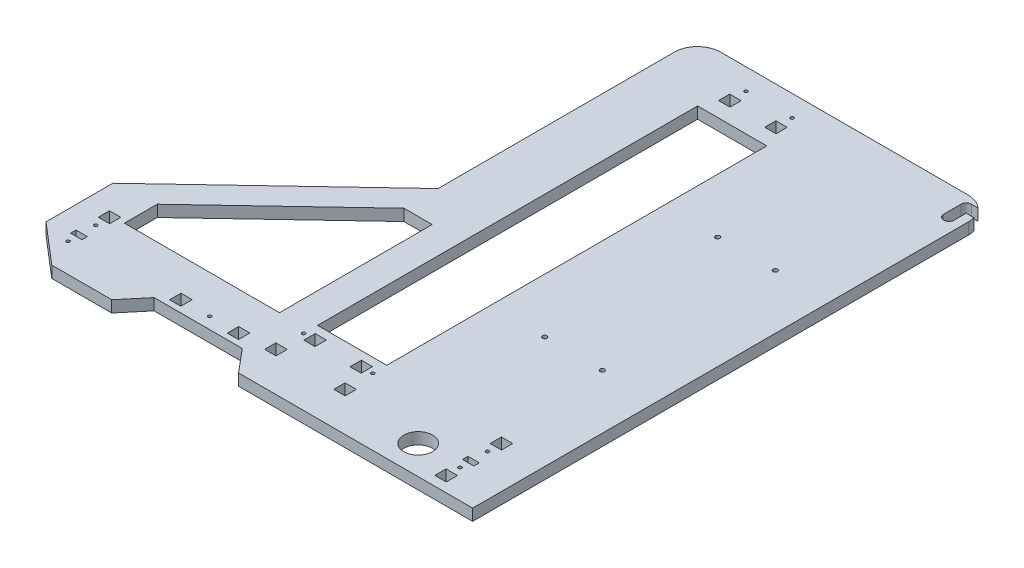
SolidWorks part; units mm, degrees
ref_plane "Front Plane" through (0, 0, 0) normal (0, 0, 1) x (1, 0, 0)
ref_plane "Top Plane" through (0, 0, 0) normal (0, 1, 0) x (1, 0, 0)
ref_plane "Right Plane" through (0, 0, 0) normal (1, 0, 0) x (0, 0, -1)
sketch "Sketch1" plane through (0, 0, 0) normal (0, 1, 0) x (1, 0, 0)
  line L0 (0, 0) -> (-235, 0)
  line L1 (-235, 0) -> (-235, -225)
  line L2 (-235, -225) -> (-380, -362)
  line L3 (-380, -362) -> (-380, -420)
  line L4 (-380, -420) -> (-345, -450)
  line L5 (-345, -450) -> (-293, -450)
  line L6 (-293, -450) -> (-263.6315, -415)
  line L7 (-263.6315, -415) -> (-212.3685, -415)
  line L8 (-212.3685, -415) -> (-183, -450)
  line L9 (-183, -450) -> (0, -450)
  line L10 (0, 0) -> (0, -450)
  line L12 (-293, -450) -> (-183, -450) construction
  dimension "D3" = 235
  dimension "D5" = 58
  dimension "D13" = 190
  dimension "D7" = 35
  dimension "D15" = 52
  dimension "D12" = 30
  dimension "D10" = 35
  dimension "D6" = 380
  dimension "D4" = 450
  dimension "D2" = 50
  dimension "D8" = 50
  dimension "D9" = 110
extrude "Boss-Extrude1" add sketch "Sketch1" along normal blind 10
sketch "Sketch16" plane through (0, 10, 0) normal (0, 1, 0) x (1, 0, 0)
  line L0 (0, -450) -> (20, -450)
  line L1 (20, -450) -> (20, 0)
  line L2 (20, 0) -> (0, 0)
  line L3 (0, 0) -> (0, -450)
  dimension "D1" = 20
  dimension "D2" = 90
extrude "Boss-Extrude2" add sketch "Sketch16" against normal through all
sketch "Sketch2" plane through (0, 10, 0) normal (0, 1, 0) x (1, 0, 0)
  line L0 (-235, -225) -> (-235, -415) construction
  line L1 (-263.6315, -415) -> (-212.3685, -415) construction
  line L2 (-345, -450) -> (-345, -328.931) construction
  line L3 (-235, -225) -> (-380, -362) construction
  line L4 (-345, -358.5097) -> (-235, -254.5787)
  line L5 (-235, -254.5787) -> (-210.5, -254.5787)
  line L6 (-210.5, -254.5787) -> (-210.5, -387)
  line L7 (-210.5, -387) -> (-345, -387)
  line L8 (-345, -387) -> (-345, -358.5097)
  line L9 (0, -450) -> (0, 0) construction
  line L10 (-184.5, -380) -> (-124.5, -380)
  line L11 (-184.5, -380) -> (-184.5, -50.425)
  line L12 (-184.5, -50.425) -> (-124.5, -50.425)
  line L13 (-124.5, -380) -> (-124.5, -50.425)
  line L14 (-124.5, -392.1) -> (-184.5, -392.1) construction
  line L15 (-16, -450) -> (-16, 0) construction
  line L16 (20, 0) -> (-235, 0) construction
  line L17 (-355.9, -440.6571) -> (-355.9, -339.2297) construction
  line L18 (-20.925, -441.85) -> (-11.075, -441.85)
  line L19 (-20.925, -441.85) -> (-20.925, -432.15)
  line L20 (-20.925, -432.15) -> (-11.075, -432.15)
  line L21 (-11.075, -441.85) -> (-11.075, -432.15)
  line L22 (-20.925, -441.85) -> (-11.075, -432.15) construction
  line L23 (-20.925, -432.15) -> (-11.075, -441.85) construction
  line L24 (-20.925, -417.85) -> (-11.075, -417.85)
  line L25 (-20.925, -417.85) -> (-20.925, -408.15)
  line L26 (-20.925, -408.15) -> (-11.075, -408.15)
  line L27 (-11.075, -417.85) -> (-11.075, -408.15)
  line L28 (-20.925, -417.85) -> (-11.075, -408.15) construction
  line L29 (-20.925, -408.15) -> (-11.075, -417.85) construction
  line L30 (-380, -420) -> (-345, -450) construction
  line L32 (-350.975, -408.15) -> (-360.825, -408.15)
  line L33 (-350.975, -408.15) -> (-350.975, -417.85)
  line L34 (-350.975, -417.85) -> (-360.825, -417.85)
  line L35 (-360.825, -408.15) -> (-360.825, -417.85)
  line L36 (-350.975, -408.15) -> (-360.825, -417.85) construction
  line L37 (-350.975, -417.85) -> (-360.825, -408.15) construction
  line L38 (-183, -450) -> (20, -450) construction
  line L39 (-183, -450) -> (20, -450) construction
  line L40 (-173.749, -32.425) -> (-113.749, -32.425) construction
  line L41 (-154.5, -50.425) -> (-154.5, -32.425) construction
  line L42 (-179.425, -27.575) -> (-169.575, -27.575)
  line L43 (-179.425, -27.575) -> (-179.425, -37.275)
  line L44 (-179.425, -37.275) -> (-169.575, -37.275)
  line L45 (-169.575, -27.575) -> (-169.575, -37.275)
  line L46 (-179.425, -27.575) -> (-169.575, -37.275) construction
  line L47 (-179.425, -37.275) -> (-169.575, -27.575) construction
  line L48 (-129.575, -37.275) -> (-139.425, -27.575) construction
  line L49 (-129.575, -27.575) -> (-139.425, -37.275) construction
  line L50 (-139.425, -27.575) -> (-139.425, -37.275)
  line L51 (-129.575, -37.275) -> (-139.425, -37.275)
  line L52 (-129.575, -27.575) -> (-129.575, -37.275)
  line L53 (-129.575, -27.575) -> (-139.425, -27.575)
  line L54 (-174.5, -32.425) -> (-174.5, -18.425) construction
  line L55 (-134.5, -32.425) -> (-134.5, -18.425) construction
  line L56 (-154.5, -380) -> (-154.5, -450) construction
  line L57 (-174.5, -392.1) -> (-134.5, -392.1) construction
  line L58 (-129.65, -397.025) -> (-139.35, -387.175) construction
  line L59 (-179.35, -387.175) -> (-169.65, -387.175)
  line L60 (-179.35, -387.175) -> (-179.35, -397.025)
  line L61 (-179.35, -397.025) -> (-169.65, -397.025)
  line L62 (-169.65, -387.175) -> (-169.65, -397.025)
  line L63 (-179.35, -387.175) -> (-169.65, -397.025) construction
  line L64 (-179.35, -397.025) -> (-169.65, -387.175) construction
  line L65 (-129.65, -387.175) -> (-139.35, -397.025) construction
  line L66 (-139.35, -387.175) -> (-139.35, -397.025)
  line L67 (-129.65, -397.025) -> (-139.35, -397.025)
  line L68 (-129.65, -387.175) -> (-129.65, -397.025)
  line L69 (-129.65, -387.175) -> (-139.35, -387.175)
  line L70 (-119.575, -420.95) -> (-129.425, -411.25) construction
  line L71 (-189.425, -411.25) -> (-179.575, -411.25)
  line L72 (-189.425, -411.25) -> (-189.425, -420.95)
  line L73 (-189.425, -420.95) -> (-179.575, -420.95)
  line L74 (-179.575, -411.25) -> (-179.575, -420.95)
  line L75 (-189.425, -411.25) -> (-179.575, -420.95) construction
  line L76 (-189.425, -420.95) -> (-179.575, -411.25) construction
  line L77 (-119.575, -411.25) -> (-129.425, -420.95) construction
  line L78 (-129.425, -411.25) -> (-129.425, -420.95)
  line L79 (-119.575, -420.95) -> (-129.425, -420.95)
  line L80 (-119.575, -411.25) -> (-119.575, -420.95)
  line L81 (-119.575, -411.25) -> (-129.425, -411.25)
  line L82 (-360.825, -408.15) -> (-11.075, -408.15) construction
  line L83 (-350.975, -393.85) -> (-360.825, -393.85)
  line L84 (-350.975, -393.85) -> (-350.975, -384.15)
  line L85 (-350.975, -384.15) -> (-360.825, -384.15)
  line L86 (-360.825, -393.85) -> (-360.825, -384.15)
  line L87 (-350.975, -393.85) -> (-360.825, -384.15) construction
  line L88 (-350.975, -384.15) -> (-360.825, -393.85) construction
  line L89 (-11.075, -384.15) -> (-20.925, -384.15)
  line L90 (-11.075, -384.15) -> (-11.075, -393.85)
  line L91 (-11.075, -393.85) -> (-20.925, -393.85)
  line L92 (-20.925, -384.15) -> (-20.925, -393.85)
  line L93 (-11.075, -384.15) -> (-20.925, -393.85) construction
  line L94 (-11.075, -393.85) -> (-20.925, -384.15) construction
  circle A0 centre (-16, -425) radius 1.45
  circle A1 centre (-16, -401) radius 1.45
  circle A2 centre (-355.9, -425) radius 1.45
  circle A3 centre (-355.9, -401) radius 1.45
  circle A4 centre (-174.5, -18.425) radius 1.45
  circle A5 centre (-134.5, -18.425) radius 1.45
  circle A6 centre (-124.5, -392.1) radius 1.45
  circle A7 centre (-184.5, -392.1) radius 1.45
  point P25 (-16, -437)
  point P30 (-16, -413)
  point P44 (-355.9, -413)
  point P58 (-355.9, -389)
  point P61 (-174.5, -32.425)
  point P72 (-134.5, -32.425)
  point P85 (-174.5, -392.1)
  point P94 (-134.5, -392.1)
  point P95 (-184.5, -416.1)
  point P104 (-124.5, -416.1)
  point P105 (-154.5, -392.1)
  point P111 (-16, -389)
  dimension "D13" = 2.9
  dimension "D14" = 2.9
  dimension "D23" = 2.9
  dimension "D24" = 2.9
  dimension "D31" = 2.9
  dimension "D37" = 2.9
  dimension "D1" = 21.5
  dimension "D2" = 28
  dimension "D3" = 24.5
  dimension "D4" = 60
  dimension "D7" = 26
  dimension "D8" = 9.7
  dimension "D9" = 9.85
  dimension "D10" = 9.85
  dimension "D11" = 9.7
  dimension "D12" = 24
  dimension "D15" = 24
  dimension "D19" = 9.85
  dimension "D20" = 9.7
  dimension "D26" = 12
  dimension "D27" = 9.85
  dimension "D28" = 9.7
  dimension "D33" = 9.7
  dimension "D38" = 9.85
  dimension "D39" = 9.7
  dimension "D41" = 24
  dimension "D34" = 30
  dimension "D36" = 12.1
  dimension "D30" = 18
  dimension "D29" = 40
  dimension "D17" = 13
  dimension "D32" = 14
  dimension "D35" = 20
  dimension "D16" = 12
  dimension "D21" = 90
  dimension "D25" = 24
  dimension "D5" = 359.75
  dimension "D22" = 349.75
  dimension "D40" = 30
  dimension "D6" = 70
  dimension "D42" = 0
  dimension "D43" = 0
  dimension "D18" = 16
  dimension "D44" = 9.85
  dimension "D45" = 24
  dimension "D46" = 24
extrude "Cut-Extrude1" cut sketch "Sketch2" against normal through all
fillet "Fillet1" radius 20 2 edges at (-235, 5, 0) (20, 5, 0)
sketch "Sketch11" plane through (0, 10, 0) normal (0, 1, 0) x (1, 0, 0)
  line L0 (-124.5, -215.2125) -> (20, -215.2125) construction
  line L1 (20, -450) -> (20, -20) construction
  line L3 (-52.25, -215.2125) -> (-52.25, -450) construction
  line L6 (-124.5, -380) -> (-124.5, -50.425) construction
  line L8 (-183, -450) -> (20, -450) construction
  circle A0 centre (-52.25, -425) radius 12.5
  circle A1 centre (-16, -425) radius 1.45 construction
  dimension "D1" = 25
  dimension "D2" = 0
  dimension "D3" = 0
extrude "WiringHole" cut sketch "Sketch11" against normal through all
sketch "Sketch9" plane through (0, 10, 0) normal (0, 1, 0) x (1, 0, 0)
  line L0 (-52.25, -412.5) -> (-52.25, 0) construction
  line L1 (0, 0) -> (-215, 0) construction
  line L2 (-124.5, -215.2125) -> (20, -215.2125) construction
  line L3 (-124.5, -380) -> (-124.5, -50.425) construction
  line L4 (-27.25, -140.2125) -> (-27.25, -290.2125) construction
  line L6 (-77.25, -140.2125) -> (-27.25, -140.2125) construction
  line L7 (-27.25, -290.2125) -> (-77.25, -290.2125) construction
  line L8 (-77.25, -290.2125) -> (-77.25, -140.2125) construction
  line L9 (20, -450) -> (20, -20) construction
  circle A0 centre (-52.25, -425) radius 12.5 construction
  circle A1 centre (-77.25, -140.2125) radius 1.95
  circle A2 centre (-27.25, -140.2125) radius 1.95
  circle A3 centre (-27.25, -290.2125) radius 1.95
  circle A4 centre (-77.25, -290.2125) radius 1.95
  dimension "D4" = 3.9
  dimension "D1" = 50
  dimension "D2" = 150
  dimension "D5" = 25
extrude "MountingHoles-PSU" cut sketch "Sketch9" against normal through all
sketch "Sketch25" plane through (0, 10, 0) normal (0, 1, 0) x (1, 0, 0)
  line L0 (-11.075, -417.85) -> (-11.075, -408.15) construction
  line L1 (-360.825, -408.15) -> (-350.975, -408.15)
  line L2 (-360.825, -408.15) -> (-360.825, -413.15)
  line L3 (-360.825, -413.15) -> (-350.975, -413.15)
  line L4 (-350.975, -408.15) -> (-350.975, -413.15)
  line L5 (-350.975, -417.85) -> (-350.975, -408.15) construction
  line L6 (-20.925, -408.15) -> (-11.075, -408.15)
  line L7 (-20.925, -408.15) -> (-20.925, -413.15)
  line L8 (-20.925, -413.15) -> (-11.075, -413.15)
  line L9 (-11.075, -408.15) -> (-11.075, -413.15)
  dimension "D1" = 5
  dimension "D2" = 5
extrude "SlotKeyingRight" add sketch "Sketch25" against normal through all
sketch "Sketch10" [suppressed] plane through (0, 10, 0) normal (0, 1, 0) x (1, 0, 0)
  line L0 (-124.5, -215.2125) -> (20, -215.2125) construction
  line L1 (20, -450) -> (20, -20) construction
  line L2 (-52.25, -245.2125) -> (-22.25, -245.2125) construction
  line L3 (-37.25, -210.225) -> (-37.25, 0) construction
  line L4 (-52.25, -215.2125) -> (-52.25, -184.5972) construction
  line L7 (-124.5, -380) -> (-124.5, -50.425) construction
  line L8 (-52.25, -302.7125) -> (-22.25, -302.7125)
  line L9 (-52.25, -302.7125) -> (-52.25, -187.7125)
  line L10 (-52.25, -187.7125) -> (-22.25, -187.7125)
  line L11 (-22.25, -302.7125) -> (-22.25, -187.7125)
  line L12 (-52.25, -302.7125) -> (-22.25, -187.7125) construction
  line L13 (-52.25, -187.7125) -> (-22.25, -302.7125) construction
  line L15 (0, 0) -> (-215, 0) construction
  line L17 (-37.25, -210.225) -> (-37.25, -450) construction
  line L18 (-183, -450) -> (20, -450) construction
  line L19 (-64.75, -215.2125) -> (-39.75, -215.2125) construction
  line L20 (-37.25, -302.7125) -> (-37.25, -187.7125) construction
  dimension "D1" = 30
  dimension "D2" = 115
  dimension "D3" = 0
  dimension "D4" = 0
  dimension "D5" = 0
  dimension "D6" = 30
  dimension "D7" = 15
extrude "WiringSlot" [suppressed] cut sketch "Sketch10" against normal through all
sketch "CenterLines" [suppressed] plane through (0, 10, 0) normal (0, 1, 0) x (1, 0, 0)
  line L0 (-37.25, -302.7125) -> (-37.25, -187.7125) construction
  line L1 (-52.25, -302.7125) -> (-22.25, -302.7125) construction
  line L2 (-22.25, -187.7125) -> (-52.25, -187.7125) construction
  line L3 (-52.25, -245.2125) -> (-22.25, -245.2125) construction
  line L4 (-52.25, -187.7125) -> (-52.25, -302.7125) construction
  line L5 (-22.25, -302.7125) -> (-22.25, -187.7125) construction
ref_plane "Plane1" [suppressed] through (-37.25, 0, 0) normal (1, 0, 0) x (0, 0, -1)
sketch "Sketch6" [suppressed] plane through (0, 10, 0) normal (0, 1, 0) x (1, 0, 0)
  line L0 (-37.25, -302.7125) -> (-37.25, -187.7125) construction
  line L1 (-61.35, -242.7125) -> (-13.15, -242.7125) construction
  line L2 (-13.15, -197.9625) -> (-13.15, -280.4625) construction
  line L3 (-52.25, -302.7125) -> (-22.25, -302.7125) construction
  line L4 (-52.25, -240.2125) -> (-22.25, -240.2125) construction
  line L5 (-22.25, -187.7125) -> (-52.25, -187.7125) construction
  line L6 (-13.15, -197.9625) -> (-13.15, -204.9625) construction
  line L7 (-11.7, -197.9625) -> (-11.7, -204.9625)
  line L8 (-14.6, -197.9625) -> (-14.6, -204.9625)
  line L9 (-52.25, -245.2125) -> (-22.25, -245.2125) construction
  line L10 (-52.25, -187.7125) -> (-52.25, -302.7125) construction
  line L11 (-22.25, -302.7125) -> (-22.25, -187.7125) construction
  line L12 (-13.15, -287.4625) -> (-13.15, -280.4625) construction
  line L13 (-14.6, -287.4625) -> (-14.6, -280.4625)
  line L14 (-61.35, -280.4625) -> (-61.35, -204.9625) construction
  line L15 (-13.15, -287.4625) -> (-13.15, -204.9625) construction
  line L16 (-11.7, -287.4625) -> (-11.7, -280.4625)
  arc A2 (-11.7, -197.9625) -> (-14.6, -197.9625) centre (-13.15, -197.9625) ccw
  arc A3 (-14.6, -204.9625) -> (-11.7, -204.9625) centre (-13.15, -204.9625) ccw
  circle A4 centre (-61.35, -280.4625) radius 1.45
  circle A6 centre (-61.35, -204.9625) radius 1.45
  arc A8 (-14.6, -287.4625) -> (-11.7, -287.4625) centre (-13.15, -287.4625) ccw
  arc A9 (-11.7, -280.4625) -> (-14.6, -280.4625) centre (-13.15, -280.4625) ccw
  point P20 (-13.15, -201.4625)
  point P25 (-13.15, -283.9625)
  dimension "D8" = 2.9
  dimension "D12" = 2.9
  dimension "D4" = 1.45
  dimension "D5" = 1.45
  dimension "D11" = 82.5
  dimension "D14" = 75.5
  dimension "D2" = 24.1
  dimension "D3" = 48.2
  dimension "D6" = 2.5
  dimension "D9" = 7
  dimension "D10" = 7
extrude "MountingHoles-RAMPS" [suppressed] cut sketch "Sketch6" against normal through all
mirror "Mirror1" [suppressed] about plane through (-37.25, 0, 0) normal (1, 0, 0)
sketch "Sketch5" [suppressed] plane through (0, 10, 0) normal (0, 1, 0) x (1, 0, 0)
  line L0 (-22.25, -245.2125) -> (-52.25, -245.2125) construction
  line L3 (-22.25, -302.7125) -> (-22.25, -187.7125) construction
  line L5 (-52.25, -187.7125) -> (-52.25, -302.7125) construction
  line L7 (-16.25, -144.7125) -> (-58.25, -144.7125) construction
  line L8 (-16.25, -345.7125) -> (-58.25, -345.7125) construction
  line L9 (-37.25, -245.2125) -> (-37.25, -144.7125) construction
  line L10 (-37.25, -245.2125) -> (-37.25, -345.7125) construction
  circle A0 centre (-58.25, -144.7125) radius 1.45
  circle A1 centre (-16.25, -144.7125) radius 1.45
  circle A2 centre (-16.25, -345.7125) radius 1.45
  circle A3 centre (-58.25, -345.7125) radius 1.45
  point P17 (-37.25, -144.7125)
  point P22 (-37.25, -345.7125)
  dimension "D2" = 2.9
  dimension "D5" = 2.9
  dimension "D6" = 2.9
  dimension "D7" = 2.9
  dimension "D3" = 201
  dimension "D4" = 100.5
  dimension "D8" = 21
  dimension "D9" = 21
  dimension "D10" = 100.5
extrude "MountingHoles-Melzi" [suppressed] cut sketch "Sketch5" against normal through all
sketch "Sketch13" [suppressed] plane through (0, 0, 0) normal (0, -1, 0) x (-1, 0, 0)
  line L0 (52.25, -215.2125) -> (124.5, -215.2125) construction
  line L1 (124.5, -380) -> (124.5, -50.425) construction
  line L2 (82.25, -264.7275) -> (82.25, -165.6975) construction
  line L3 (37.25, -302.7125) -> (37.25, -187.7125) construction
  line L4 (52.25, -187.7125) -> (52.25, -302.7125) construction
  line L6 (82.25, -264.7275) -> (-15.65, -264.7275) construction
  circle A0 centre (82.25, -165.6975) radius 1.45
  circle A1 centre (82.25, -264.7275) radius 1.45
  circle A2 centre (-10.59, -172.1775) radius 1.45
  circle A3 centre (-15.65, -264.7275) radius 1.45
  point P11 (82.25, -215.2125)
  dimension "D8" = 2.9
  dimension "D6" = 2.9
  dimension "D1" = 2.9
  dimension "D2" = 49.515
  dimension "D3" = 45
  dimension "D4" = 6.48
  dimension "D5" = 92.84
  dimension "D7" = 97.9
extrude "Mountingholes-Smoothieboard" [suppressed] cut sketch "Sketch13" against normal through all
mirror "Flipped" [suppressed] about plane through (-37.25, 0, 0) normal (1, 0, 0)
sketch "Sketch21" [suppressed] plane through (0, 10, 0) normal (0, 1, 0) x (1, 0, 0)
  line L0 (-37.25, -187.7125) -> (-37.25, 0) construction
  line L1 (-22.25, -187.7125) -> (-52.25, -187.7125) construction
  line L2 (0, 0) -> (-215, 0) construction
  line L3 (-37.25, -85) -> (-23.3697, -85) construction
  circle A0 centre (-12.75, -56) radius 1.45
  circle A1 centre (-61.75, -56) radius 1.45
  circle A2 centre (-61.75, -114) radius 1.45
  circle A3 centre (-12.75, -114) radius 1.45
  dimension "D1" = 2.9
  dimension "D2" = 24.5
  dimension "D3" = 29
  dimension "D4" = 85
extrude "Pi" [suppressed] cut sketch "Sketch21" against normal through all
sketch "Sketch24" [suppressed] plane through (0, 10, 0) normal (0, 1, 0) x (1, 0, 0)
  line L0 (-350.975, -393.85) -> (-350.975, -384.15) construction
  line L1 (-11.075, -441.85) -> (-11.075, -432.15) construction
  line L2 (-20.925, -432.15) -> (-11.075, -432.15)
  line L3 (-360.825, -384.15) -> (-350.975, -384.15)
  line L4 (-360.825, -384.15) -> (-360.825, -389.15)
  line L5 (-360.825, -389.15) -> (-350.975, -389.15)
  line L6 (-350.975, -384.15) -> (-350.975, -389.15)
  line L7 (-20.925, -432.15) -> (-20.925, -437.15)
  line L8 (-20.925, -437.15) -> (-11.075, -437.15)
  line L9 (-11.075, -432.15) -> (-11.075, -437.15)
  line L10 (-169.575, -37.275) -> (-169.575, -27.575) construction
  line L11 (-179.425, -27.575) -> (-169.575, -27.575)
  line L12 (-179.425, -27.575) -> (-179.425, -29.575)
  line L13 (-179.425, -29.575) -> (-169.575, -29.575)
  line L14 (-169.575, -27.575) -> (-169.575, -29.575)
  line L15 (-129.575, -37.275) -> (-129.575, -27.575) construction
  line L16 (-139.425, -27.575) -> (-129.575, -27.575)
  line L17 (-139.425, -27.575) -> (-139.425, -29.575)
  line L18 (-139.425, -29.575) -> (-129.575, -29.575)
  line L19 (-129.575, -27.575) -> (-129.575, -29.575)
  line L20 (-169.575, -29.575) -> (-139.425, -29.575) construction
  dimension "D1" = 5
  dimension "D2" = 5
  dimension "D3" = 2
extrude "SlotKeyingLeft" [suppressed] add sketch "Sketch24" against normal through all
sketch "Sketch17" plane through (0, 10, 0) normal (0, 1, 0) x (1, 0, 0)
  line L0 (0, 0) -> (20, 0) construction
  line L1 (20, -23.6361) -> (20, 0) construction
  line L2 (20, -450) -> (20, -20) construction
  line L3 (20, -10) -> (8, -10) construction
  line L4 (20, -14.5) -> (8, -14.5)
  line L5 (20, -5.5) -> (8, -5.5)
  arc A0 (20, -14.5) -> (20, -5.5) centre (20, -10) ccw
  arc A1 (8, -5.5) -> (8, -14.5) centre (8, -10) ccw
  point P8 (14, -10)
  dimension "D1" = 9
  dimension "D2" = 12
  dimension "D3" = 10
extrude "Cut-Extrude3" cut sketch "Sketch17" against normal through all
sketch "Sketch18" plane through (0, 10, 0) normal (0, 1, 0) x (1, 0, 0)
  line L0 (8, -5.5) -> (8, -14.5) construction
  line L1 (3.5, -10) -> (8, -10) construction
  line L2 (8, -10) -> (8, -25) construction
  line L3 (12.5, -10) -> (12.5, -25)
  line L4 (3.5, -10) -> (3.5, -25)
  arc A0 (8, -5.5) -> (8, -14.5) centre (8, -10) ccw construction
  arc A1 (12.5, -10) -> (3.5, -10) centre (8, -10) ccw
  arc A2 (3.5, -25) -> (12.5, -25) centre (8, -25) ccw
  point P10 (8, -17.5)
  dimension "D1" = 9
  dimension "D2" = 0
  dimension "D3" = 15
extrude "Cut-Extrude4" cut sketch "Sketch18" against normal through all
sketch "Sketch19" plane through (0, 10, 0) normal (0, 1, 0) x (1, 0, 0)
  line L0 (-2, -25) -> (18, -25) construction
  line L1 (8, -25) -> (8, -5.5) construction
  circle A0 centre (18, -25) radius 1.45
  arc A1 (8, -5.5) -> (3.5, -10) centre (8, -10) ccw construction
  circle A2 centre (-2, -25) radius 1.45
  dimension "D2" = 2.9
extrude "Cut-Extrude5" [suppressed] cut sketch "Sketch19" against normal through all
sketch "Sketch22" plane through (0, 10, 0) normal (0, 1, 0) x (1, 0, 0)
  line L0 (-276.218, -430) -> (-199.782, -430)
  line L1 (-293, -450) -> (-263.6315, -415) construction
  line L2 (-212.3685, -415) -> (-183, -450) construction
  line L3 (-199.782, -430) -> (-212.3685, -415)
  line L4 (-212.3685, -415) -> (-263.6315, -415)
  line L5 (-263.6315, -415) -> (-276.218, -430)
  dimension "D1" = 15
extrude "Boss-Extrude3" add sketch "Sketch22" against normal through all
sketch "Sketch23" plane through (0, 10, 0) normal (0, 1, 0) x (1, 0, 0)
  line L0 (-238, -430) -> (-238, -387) construction
  line L1 (-276.218, -430) -> (-199.782, -430) construction
  line L2 (-345, -387) -> (-210.5, -387) construction
  line L3 (-213, -420) -> (-263, -420) construction
  line L4 (-179.35, -387.175) -> (-179.35, -397.025) construction
  line L5 (-267.85, -415.075) -> (-258.15, -415.075)
  line L6 (-267.85, -415.075) -> (-267.85, -424.925)
  line L7 (-267.85, -424.925) -> (-258.15, -424.925)
  line L8 (-258.15, -415.075) -> (-258.15, -424.925)
  line L9 (-267.85, -415.075) -> (-258.15, -424.925) construction
  line L10 (-267.85, -424.925) -> (-258.15, -415.075) construction
  line L11 (-208.15, -424.925) -> (-217.85, -415.075) construction
  line L12 (-208.15, -415.075) -> (-217.85, -424.925) construction
  line L13 (-217.85, -415.075) -> (-217.85, -424.925)
  line L14 (-208.15, -424.925) -> (-217.85, -424.925)
  line L15 (-208.15, -415.075) -> (-208.15, -424.925)
  line L16 (-208.15, -415.075) -> (-217.85, -415.075)
  circle A0 centre (-238, -420) radius 1.45
  point P19 (-238, -420)
  dimension "D4" = 2.9
  dimension "D1" = 9.7
  dimension "D3" = 10
extrude "Cut-Extrude6" cut sketch "Sketch23" against normal through all
equation "\"Y-ROD-SPACING\"=75"
equation "\"Y-BED-OFFSET\"=2"
equation "\"Y-BED-ROD-INSET\"=3.5"
equation "\"T-SLOT-NUT-FILLET-RADIUS\"=0.5"
equation "\"T-SLOT-SCREW-SHAFT-RADIUS\"=1.55"
equation "\"T-SLOT-SCREW-SHAFT-CUTOUT-LENGTH\"=11"
equation "\"T-SLOT-NUT-DEPTH\"=3.5"
equation "\"T-SLOT-NUT-WIDTH\"=2.85"
equation "\"T-SLOT-NUT-END-DISTANCE\"=8"
equation "\"ACRYLIC-TAB-CUTOUT-SIZE\"=\"ACRYLIC-THICKNESS\"+\"ACRYLIC-TAB-TOLERANCE\"*2"
equation "\"ACRYLIC-TAB-WIDTH\"=\"ACRYLIC-THICKNESS\""
equation "\"ACRYLIC-M3-HOLE\"=2.9"
equation "\"SMOOTHROD-CAP-SCREW-DISTANCE\"=20"
equation "\"FRAME-WIDTH-INNER\"=370"
equation "\"D24@Sketch2\"=\"ACRYLIC-M3-HOLE\""
equation "\"D23@Sketch2\"=\"ACRYLIC-M3-HOLE\""
equation "\"D19@Sketch2\"=\"ACRYLIC-THICKNESS\"-\"KERF\"*2"
equation "\"D20@Sketch2\"=\"ACRYLIC-TAB-WIDTH\"-\"KERF\"*4"
equation "\"D37@Sketch2\"=\"ACRYLIC-M3-HOLE\""
equation "\"D33@Sketch2\"=\"ACRYLIC-TAB-WIDTH\"-\"KERF\"*4"
equation "\"D38@Sketch2\"=\"ACRYLIC-THICKNESS\"-\"KERF\"*2"
equation "\"D39@Sketch2\"=\"ACRYLIC-TAB-WIDTH\"-\"KERF\"*4"
equation "\"D13@Sketch2\"=\"ACRYLIC-M3-HOLE\""
equation "\"D14@Sketch2\"=\"ACRYLIC-M3-HOLE\""
equation "\"D8@Sketch2\"=\"ACRYLIC-TAB-WIDTH\"-\"KERF\"*4"
equation "\"D9@Sketch2\"=\"ACRYLIC-THICKNESS\"-\"KERF\"*2"
equation "\"D10@Sketch2\"=\"ACRYLIC-THICKNESS\"-\"KERF\"*2"
equation "\"D11@Sketch2\"=\"ACRYLIC-TAB-WIDTH\"-\"KERF\"*4"
equation "\"D31@Sketch2\"=\"ACRYLIC-M3-HOLE\""
equation "\"D27@Sketch2\"=\"ACRYLIC-THICKNESS\"-\"KERF\"*2"
equation "\"D28@Sketch2\"=\"ACRYLIC-TAB-WIDTH\"-\"KERF\"*4"
equation "\"NEMA17-HOLE-SPACING\"=31"
equation "\"NEMA17-CENTRAL-CUTOUT\"=22.5"
equation "\"Z-BRACKET-REACH\"=57"
equation "\"TOP-BRACKET-SPACING\"=40"
equation "\"D29@Sketch2\"=\"TOP-BRACKET-SPACING\""
equation "\"ACRYLIC-THICKNESS\"=10"
equation "\"SMOOTHROD-Z-LENGTH\"=350"
equation "\"D5@Sketch2\"=\"SMOOTHROD-Z-LENGTH\"-\"SMOOTHROD-TIGHTENING-HEADROOM\"+10"
equation "\"SMOOTHROD-X-LENGTH\"=350"
equation "\"SMOOTHROD-Y-LENGTH\"=350"
equation "\"D22@Sketch2\"=\"SMOOTHROD-Y-LENGTH\"-\"SMOOTHROD-TIGHTENING-HEADROOM\""
equation "\"SMOOTHROD-TIGHTENING-HEADROOM\"=.25"
equation "\"X-ROD-SPACING\"=45"
equation "\"Z-ROD-SPACING\"=17.5"
equation "\"LEADSCREW-Z-LENGTH\"=300"
equation "\"SCREW-HEAD-RADIUS\"=6"
equation "\"PRINTED-X-SMOOTHROD-DIAMETER\"=8.8"
equation "\"PRINTED-X-SMOOTHROD-CUTOUT\"=10"
equation "\"PRINTED-X-BASE-HEIGHT\"=10"
equation "\"PRINTED-LM8UU-CUTOUT-SIZE\"=15.5"
equation "\"PRINTED-LM8UU-CUTOUT-LENGTH\"=24.5"
equation "\"PRINTED-X-IDLER-HEIGHT\"=16"
equation "\"PSU-MOUNTING-WIDTH\"=50"
equation "\"PSU-MOUNTING-HEIGHT\"=150"
equation "\"D1@Sketch9\"=\"PSU-MOUNTING-WIDTH\""
equation "\"D1@Boss-Extrude1\"=\"ACRYLIC-THICKNESS\""
equation "\"D6@Sketch1\"=\"SMOOTHROD-Y-LENGTH\"+30"
equation "\"D4@Sketch9\"=\"ACRYLIC-M4-HOLE\""
equation "\"D2@Sketch9\"=\"PSU-MOUNTING-HEIGHT\""
equation "\"D5@Sketch9\"=\"PSU-MOUNTING-WIDTH\"/2"
equation "\"D4@Sketch1\"=\"SMOOTHROD-Z-LENGTH\"+100"
equation "\"D8@Sketch6\"=\"ACRYLIC-M3-HOLE\""
equation "\"D12@Sketch6\"=\"ACRYLIC-M3-HOLE\""
equation "\"D2@Sketch5\"=\"ACRYLIC-M3-HOLE\""
equation "\"D5@Sketch5\"=\"ACRYLIC-M3-HOLE\""
equation "\"D6@Sketch5\"=\"ACRYLIC-M3-HOLE\""
equation "\"D7@Sketch5\"=\"ACRYLIC-M3-HOLE\""
equation "\"D1@Sketch13\"=\"ACRYLIC-M3-HOLE\""
equation "\"D6@Sketch13\"=\"ACRYLIC-M3-HOLE\""
equation "\"D8@Sketch13\"=\"ACRYLIC-M3-HOLE\""
equation "\"D4@Sketch6\"=\"ACRYLIC-M3-HOLE\"/2"
equation "\"D5@Sketch6\"=\"ACRYLIC-M3-HOLE\"/2"
equation "\"Y-BED-SCREW-SPACING\"=209"
equation "\"Y-BED-SCREW-CUTOUT-SLOT-HEIGHT\"=2.5"
equation "\"ACRYLIC-THICKNESS2\"=4.5"
equation "\"ACRYLIC-TAB-TOLERANCE\"=-.05"
equation "\"Z-ROD-INSET\"=13.5"
equation "\"SCREW-LENGTH-FRAME\"=\"ACRYLIC-THICKNESS\" + 10"
equation "\"SCREW-LENGTH-MOTOR\"=\"ACRYLIC-THICKNESS\" + 5"
equation "\"SCREW-LENGTH-EXTRUDER\"=28"
equation "\"Y-BELT-TO-ROD-DISTANCE\"=20"
equation "\"SPOOL-HOLDER-ROD-SPACING\"=150"
equation "\"ACRYLIC-X-CARRIAGE-WIDTH\"=55"
equation "\"ACRYLIC-X-CARRIAGE-HEIGHT\"=75"
equation "\"ACRYLIC-X-CARRIAGE-LM8UU-CUTOUT-WIDTH\"=24.25"
equation "\"ACRYLIC-X-CARRIAGE-SCREW-SPACING-X\"=15"
equation "\"ACRYLIC-X-CARRIAGE-SCREW-SPACING-Y\"=33"
equation "\"ACRYLIC-X-CARRIAGE-CENTER-TAB-SPACING\"=14"
equation "\"ACRYLIC-X-CARRIAGE-EXTRUDER-OFFSET\"=26"
equation "\"ACRYLIC-X-CARRIAGE-EXTRUDER-ANGLE\"=90"
equation "\"ACRYLIC-X-CARRIAGE-EXTRUDER-SHELF-DEPTH\"=\"ACRYLIC-X-CARRIAGE-EXTRUDER-OFFSET\" + 28"
equation "\"ACRYLIC-X-CARRIAGE-EXTRUDER-BRACE-SPACING\"=23"
equation "\"ACRYLIC-X-CARRIAGE-EXTRUDER-BRACE-TAB-OFFSET\"=20"
equation "\"ACRYLIC-X-CARRIAGE-EXTRUDER-BRACE-HEIGHT\"=35"
equation "\"ACRYLIC-X-CARRIAGE-EXTRUDER-BRACE-SCREW-SPACING\"=22"
equation "\"D1@Sketch19\"=\"SMOOTHROD-CAP-SCREW-DISTANCE\"/2"
equation "\"D2@Sketch19\"=\"ACRYLIC-M3-HOLE\""
equation "\"D1@Sketch21\"=\"ACRYLIC-M3-HOLE\""
equation "\"KERF\"=0.075"
equation "\"PRINTED-M3-HOLE\"=3.5"
equation "\"PRINTED-M3-NUT-AF\"=6.25"
equation "\"ACRYLIC-X-CARRIAGE-LM8UU-CUTOUT-HEIGHT\"=11.0"
equation "\"ACRYLIC-X-CARRIAGE-DUAL-WIDTH-MULTIPLIER\"=1.65"
equation "\"ACRYLIC-X-CARRIAGE-DUAL-HOTEND-SPACING\"=42"
equation "\"ACRYLIC-X-CARRIAGE-DUAL-WIDTH\"=75"
equation "\"ACRYLIC-X-CARRIAGE-DUAL-FAN-OFFSET\"=52"
equation "\"ACRYLIC-X-CARRIAGE-DUAL-FAN-HEIGHT\"=20"
equation "\"ACRYLIC-X-CARRIAGE-DUAL-HOTEND-SEPARATION\"=36"
equation "\"ACRYLIC-X-CARRIAGE-DUAL-MOUNT-PLATE-DEPTH\"=75"
equation "\"ACRYLIC-X-CARRIAGE-DUAL-MOUNT-BRACE-WIDTH\"=33"
equation "\"ACRYLIC-X-CARRIAGE-DUAL-MOUNT-SCREW-WIDTH\"=40"
equation "\"BLOWER-FAN-WIDTH\"=15"
equation "\"D44@Sketch2\"=\"ACRYLIC-THICKNESS\"-\"KERF\"*2"
equation "\"D1@Sketch23\"=10-\"KERF\"*4"
equation "\"D4@Sketch23\"=\"ACRYLIC-M3-HOLE\""
equation "\"ACRYLIC-THICKNESS-TAB-CUTOUT-WIDTH\"=\"ACRYLIC-THICKNESS\"-\"KERF\"*2"
equation "\"ACRYLIC-THICKNESS-TAB-CUTOUT-HEIGHT\"=\"ACRYLIC-TAB-WIDTH\"-\"KERF\"*4"
equation "\"ACRYLIC-THICKNESS2-TAB-CUTOUT-WIDTH\"=\"ACRYLIC-THICKNESS2\"-\"KERF\"*2"
equation "\"ACRYLIC-THICKNESS2-TAB-CUTOUT-HEIGHT\"=\"ACRYLIC-TAB-WIDTH\"-\"KERF\"*4"
equation "\"ACRYLIC-M4-HOLE\"=3.9"
